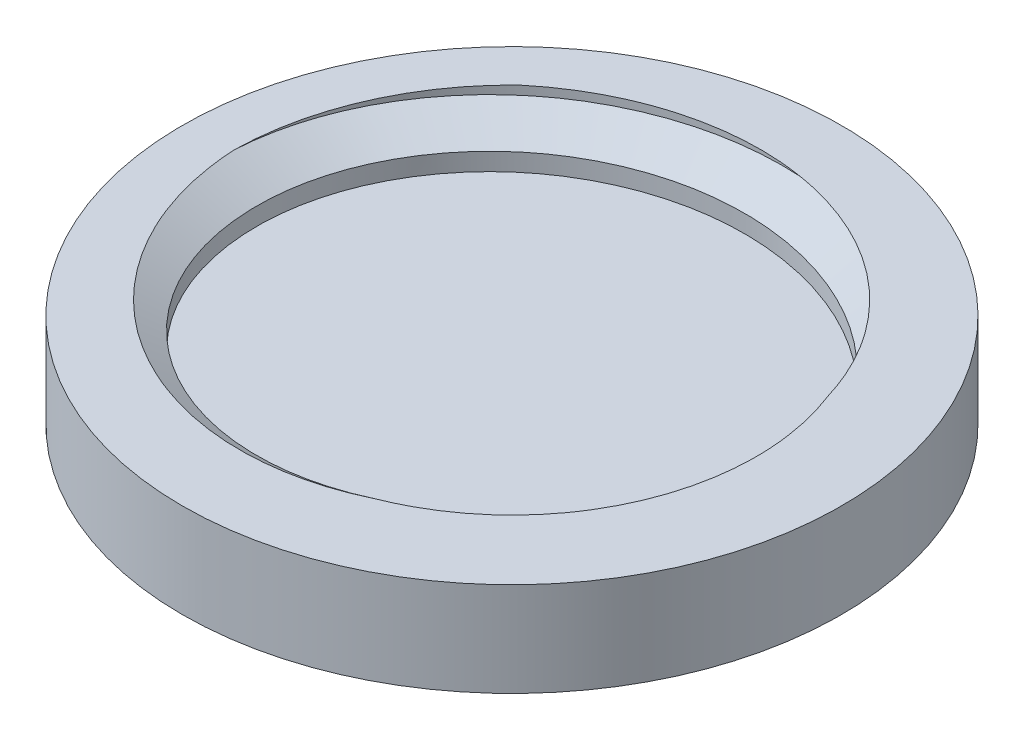
SolidWorks part; units mm, degrees
ref_plane "Front Plane" through (0, 0, 0) normal (0, 0, 1) x (1, 0, 0)
ref_plane "Top Plane" through (0, 0, 0) normal (0, 1, 0) x (1, 0, 0)
ref_plane "Right Plane" through (0, 0, 0) normal (1, 0, 0) x (0, 0, -1)
sketch "Sketch1" plane through (0, 0, 0) normal (0, 1, 0) x (1, 0, 0)
  circle A0 centre (0, 0) radius 14
extrude "Boss-Extrude1" add sketch "Sketch1" along normal blind 4
sketch "Sketch13" plane through (0, 4, 0) normal (0, 1, 0) x (1, 0, 0)
  circle A0 centre (0, 0) radius 12
extrude "Cut-Extrude1" cut sketch "Sketch13" against normal blind 3
thread "Thread2" pitch 3 method extrude trim with start face yes trim with end face yes profile "Thread Profile4" start angle 1, offset 3, length 6, pitch 3, diameter 24
ref_plane "Plane4" through (-11.9982, 7, -0.2094) normal (-0.0175, 0, 0.9998) x (-0.9998, 0, -0.0175)
sketch "Thread Profile4" plane through (-11.9982, 7, -0.2094) normal (-0.0175, 0, 0.9998) x (-0.9998, 0, -0.0175)
  line L0 (0, 0) -> (0, 3) construction
  line L11 (0, 0) -> (0, 2.625)
  line L12 (0, 2.625) -> (-1.6238, 1.6875)
  line L13 (-1.6238, 1.6875) -> (-1.6238, 0.9375)
  line L15 (-1.6238, 0.9375) -> (0, 0)
  line L17 (-1.6238, 1.3125) -> (0, 1.3125) construction
  point P2 (0, 0)
  dimension "Pitch" = 3
  dimension "Profile_Angle" = 60
  dimension "Profile_Land" = 0.75
  dimension "Profile_Height" = 1.6238
